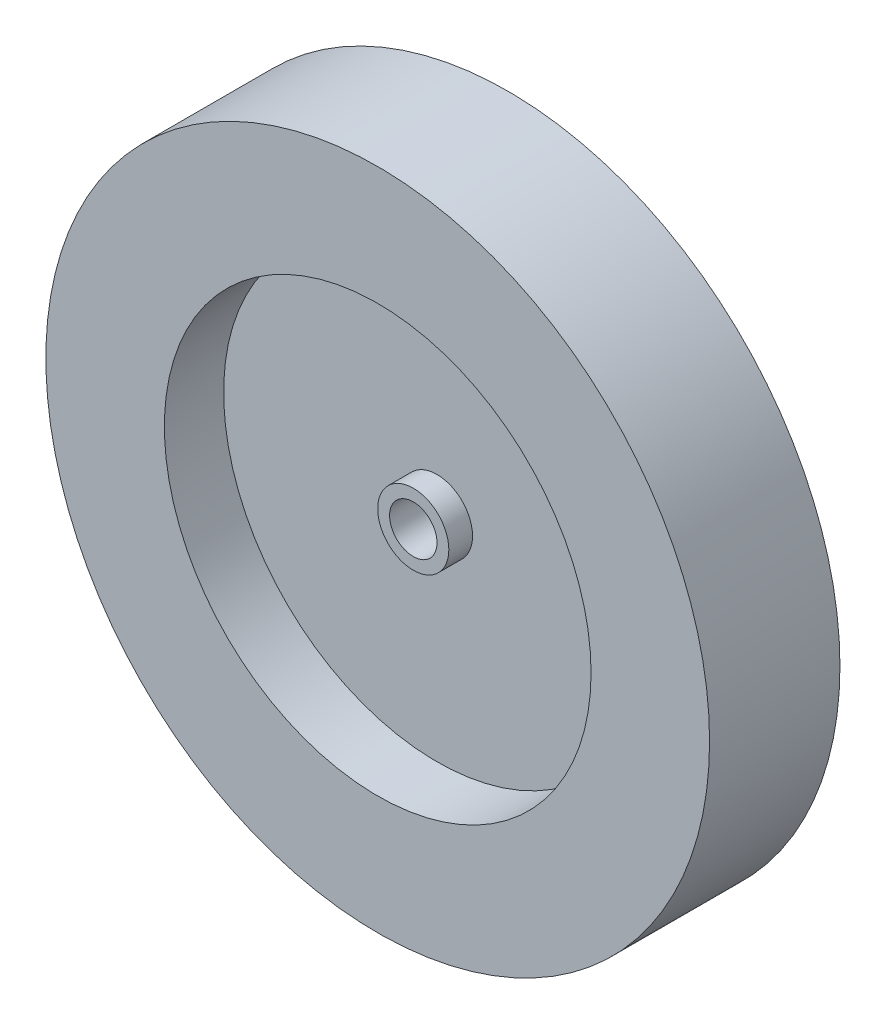
SolidWorks part; units mm, degrees
material "ABS"
ref_plane "Front Plane" through (0, 0, 0) normal (0, 0, 1) x (1, 0, 0)
ref_plane "Top Plane" through (0, 0, 0) normal (0, 1, 0) x (1, 0, 0)
ref_plane "Right Plane" through (0, 0, 0) normal (1, 0, 0) x (0, 0, -1)
sketch "Sketch1" plane through (0, 0, 0) normal (0, 0, 1) x (1, 0, 0)
  circle A0 centre (0, 0) radius 88.9
  circle A1 centre (0, 0) radius 69.85
extrude "Boss-Extrude1" add sketch "Sketch1" along normal mid plane 34.925
sketch "Sketch2" plane through (0, 0, 0) normal (0, 0, 1) x (1, 0, 0)
  circle A0 centre (0, 0) radius 69.85
extrude "Boss-Extrude2" add sketch "Sketch2" along normal mid plane 3.175
sketch "Sketch3" plane through (0, 0, 0) normal (0, 0, 1) x (1, 0, 0)
  circle A0 centre (0, 0) radius 69.85
  circle A1 centre (0, 0) radius 57.15
extrude "Boss-Extrude3" add sketch "Sketch3" along normal mid plane 34.925 separate body
sketch "Sketch4" plane through (0, 0, 0) normal (0, 0, 1) x (1, 0, 0)
  circle A0 centre (0, 0) radius 9.525
extrude "Boss-Extrude4" add sketch "Sketch4" along normal blind 7.9375
sketch "Sketch5" plane through (0, 0, 0) normal (0, 0, 1) x (1, 0, 0)
  circle A0 centre (0, 0) radius 9.525
extrude "Boss-Extrude5" add sketch "Sketch5" against normal blind 25.4
sketch "Sketch6" plane through (0, 0, 0) normal (0, 0, 1) x (1, 0, 0)
  circle A0 centre (0, 0) radius 6.35
extrude "Cut-Extrude1" cut sketch "Sketch6" against normal through all both and the other way through all
